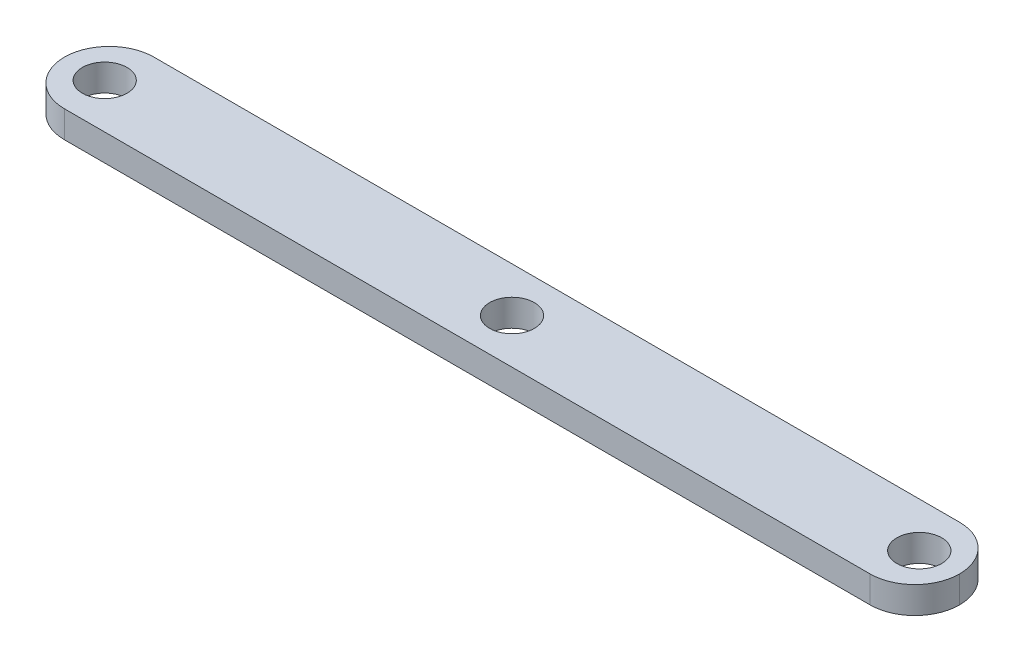
SolidWorks part; units mm, degrees
ref_plane "Front Plane" through (0, 0, 0) normal (0, 0, 1) x (1, 0, 0)
ref_plane "Top Plane" through (0, 0, 0) normal (0, 1, 0) x (1, 0, 0)
ref_plane "Right Plane" through (0, 0, 0) normal (1, 0, 0) x (0, 0, -1)
sketch "Sketch2" plane through (0, 0, 0) normal (0, 1, 0) x (1, 0, 0)
  line L1 (0, 0) -> (200, 0)
  line L2 (0, 0) -> (0, 20)
  line L3 (0, 20) -> (200, 20)
  line L4 (200, 0) -> (200, 20)
  dimension "D1" = 200
  dimension "D2" = 20
extrude "Boss-Extrude1" add sketch "Sketch2" along normal blind 6
sketch "Sketch3" plane through (0, 6, 0) normal (0, 1, 0) x (1, 0, 0)
  line L0 (200, 20) -> (0, 20) construction
  line L1 (0, 20) -> (0, 0) construction
  circle A0 centre (9, 10) radius 5
  dimension "D1" = 10
  dimension "D2" = 9
extrude "Cut-Extrude1" cut sketch "Sketch3" against normal through all
sketch "Sketch4" plane through (0, 6, 0) normal (0, 1, 0) x (1, 0, 0)
  line L0 (200, 20) -> (0, 20) construction
  line L1 (200, 0) -> (200, 20) construction
  circle A0 centre (191, 10) radius 5
  dimension "D1" = 10
  dimension "D2" = 9
extrude "Cut-Extrude2" cut sketch "Sketch4" against normal through all
fillet "Fillet1" radius 10 2 edges at (0, 3, -20) (0, 3, 0)
fillet "Fillet2" radius 10 2 edges at (200, 3, -20) (200, 3, 0)
sketch "Sketch6" plane through (0, 6, 0) normal (0, 1, 0) x (1, 0, 0)
  line L0 (0, 15) -> (0, 5) construction
  line L1 (200, 5) -> (200, 15) construction
  line L2 (190, 20) -> (10, 20) construction
  line L3 (10, 0) -> (190, 0) construction
  circle A0 centre (100, 10) radius 5
  dimension "D1" = 200
  dimension "D2" = 100
  dimension "D3" = 20
  dimension "D4" = 10
extrude "Cut-Extrude3" cut sketch "Sketch6" against normal through all
